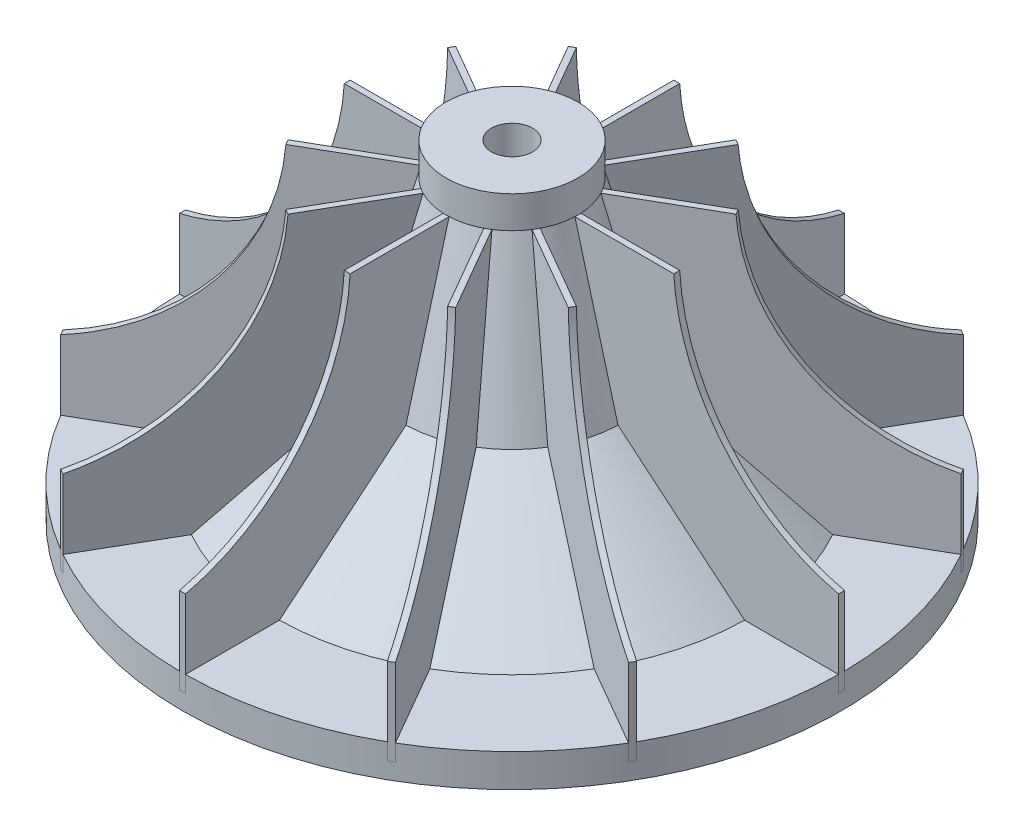
SolidWorks part; units mm, degrees
ref_plane "Front Plane" through (0, 0, 0) normal (0, 0, 1) x (1, 0, 0)
ref_plane "Top Plane" through (0, 0, 0) normal (0, 1, 0) x (1, 0, 0)
ref_plane "Right Plane" through (0, 0, 0) normal (1, 0, 0) x (0, 0, -1)
sketch "Sketch1" plane through (0, 0, 0) normal (0, 0, 1) x (1, 0, 0)
  line L7 (0, 0) -> (0, 37.1175) construction
  line L8 (0, 0) -> (-50.8, 0)
  line L9 (-50.8, 0) -> (-50.8, 5.08)
  line L10 (-36.306, 5.08) -> (-50.8, 5.08)
  line L11 (-36.306, 5.08) -> (-16.8028, 21.3522)
  line L12 (-16.8028, 21.3522) -> (-10.16, 45.8682)
  line L13 (-10.16, 45.8682) -> (-10.16, 50.8)
  line L14 (-10.16, 50.8) -> (0, 50.8)
  line L15 (0, 50.8) -> (0, 0)
  dimension "D1" = 50.8
  dimension "D2" = 10.16
  dimension "D3" = 50.8
  dimension "D4" = 5.08
  dimension "D5" = 25.4
  dimension "D6" = 25.4
  dimension "D7" = 215
revolve "Revolve1" add sketch "Sketch1" angle 360 about L7
ref_plane "Plane1" through (0, 50.8, 0) normal (0, 1, 0) x (1, 0, 0)
sketch "Sketch3" plane through (0, 50.8, 0) normal (0, 1, 0) x (1, 0, 0)
  line L6 (0.4559, -50.8) -> (0.4559, -8.89)
  line L7 (-0.4559, -50.8) -> (-0.4559, -8.89)
  line L8 (-0.4559, -8.89) -> (0.4559, -8.89)
  line L9 (-0.4559, -50.8) -> (0.4559, -50.8)
  dimension "D1" = 41.91
extrude "Boss-Extrude5" add sketch "Sketch3" against normal blind 48.26
pattern_circular "CirPattern8" count 12 over 360 about axis through (0, 5.08, 0) along (0, -1, 0) of "Boss-Extrude5"
sketch "Sketch4" plane through (0, 0, 0) normal (1, 0, 0) x (0, 0, -1)
  line L3 (-53.34, 58.5682) -> (-53.34, 15.3882)
  line L4 (-53.34, 15.3882) -> (-53.1322, 15.3882)
  line L5 (0, 0) -> (0, 72.6591) construction
  line L6 (-25.4, 45.8682) -> (-10.16, 45.8682)
  line L7 (-10.16, 45.8682) -> (-10.16, 51.0959)
  line L8 (-10.16, 51.0959) -> (-10.16, 59.6207)
  line L9 (-10.16, 59.6207) -> (-53.34, 58.5682)
  arc A0 (-53.1322, 15.3882) -> (-25.4, 45.8682) centre (-58.1589, 47.8177) ccw
  dimension "D1" = 43.18
  dimension "D2" = 10.16
revolve "Cut-Revolve1" cut sketch "Sketch4" angle 360 about L5
sketch "Sketch6" plane through (0, 50.8, 0) normal (0, 1, 0) x (1, 0, 0)
  circle A0 centre (0, 0) radius 3.175
  dimension "D1" = 6.35
extrude "Cut-Extrude1" cut sketch "Sketch6" against normal up to next
equation "\"1.90n\"=2"
